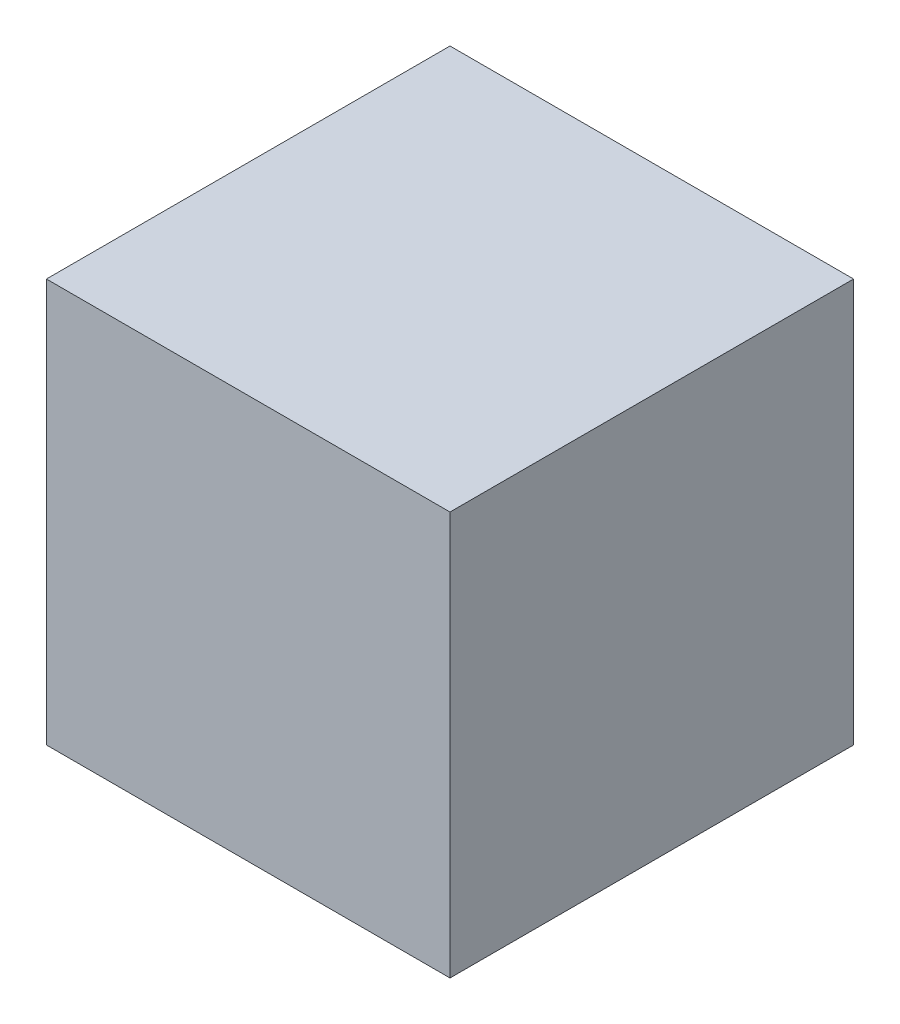
SolidWorks part; units mm, degrees
ref_plane "Front" through (0, 0, 0) normal (0, 0, 1) x (1, 0, 0)
ref_plane "Top" through (0, 0, 0) normal (0, 1, 0) x (1, 0, 0)
ref_plane "Right" through (0, 0, 0) normal (1, 0, 0) x (0, 0, -1)
sketch "Sketch1" plane through (0, 0, 0) normal (0, 0, 1) x (1, 0, 0)
  line L1 (0, 0) -> (100, 0)
  line L2 (0, 0) -> (0, 100)
  line L3 (0, 100) -> (100, 100)
  line L4 (100, 0) -> (100, 100)
extrude "Extrude1" add sketch "Sketch1" along normal blind 100
